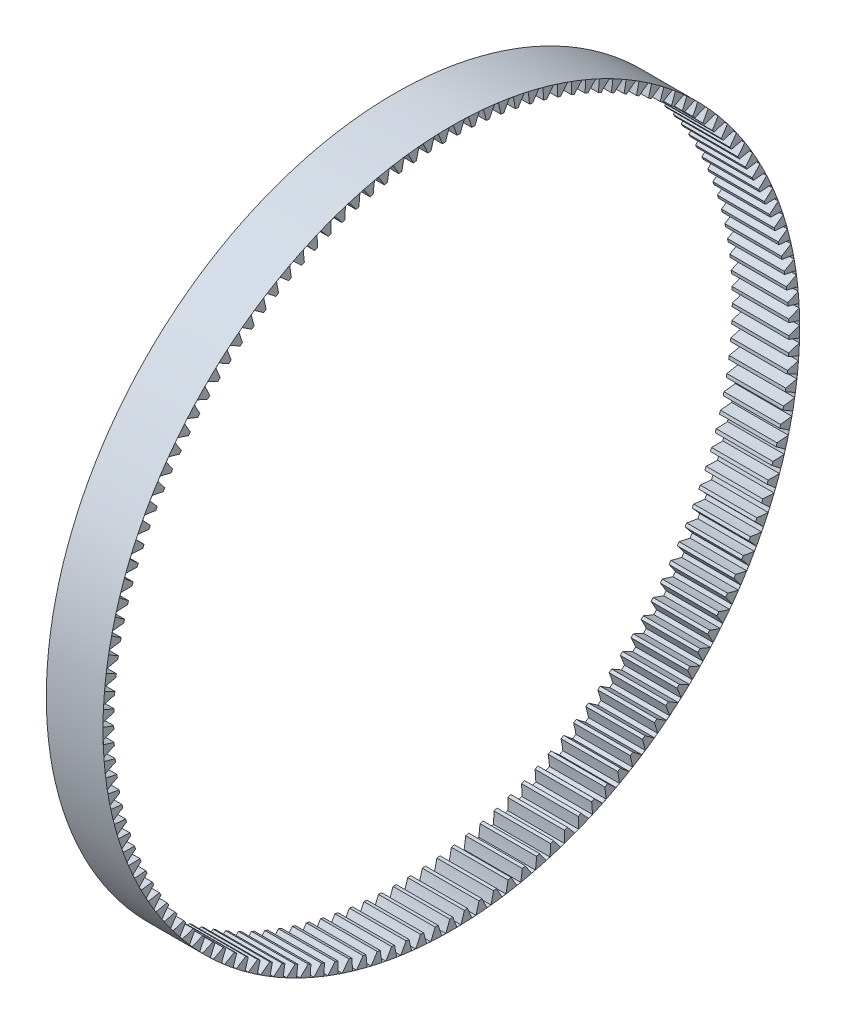
SolidWorks part; units mm, degrees
ref_plane "Plane1" through (0, 0, 0) normal (0, 0, 1) x (1, 0, 0)
ref_plane "Plane2" through (0, 0, 0) normal (0, 1, 0) x (1, 0, 0)
ref_plane "Plane3" through (0, 0, 0) normal (1, 0, 0) x (0, 0, -1)
other "Configuration Table"
sketch "HoldingSke" plane through (0, 0, 0) normal (0, 1, 0) x (1, 0, 0)
  line L0 (0, 0) -> (-0.8192, -0.5736)
  line L1 (-15, 0) -> (100, 0) construction
  line L2 (0, 0) -> (-2.1039, 2.3779)
  line L3 (0, 0) -> (-11.863, 4.5341)
  line L4 (0, 0) -> (-7.0742, 4.9534)
  line L5 (0, 0) -> (-23.7986, -8.8762)
  line L6 (0, 0) -> (-10.5278, -7.1032)
  line L7 (-2.1039, 2.3779) -> (3.3635, 27.1825)
  line L8 (-76.2, 3.3779) -> (-54.61, 3.3779)
  line L9 (-71.009, 38.7566) -> (-53.1078, 45.2721)
  line L10 (-76.2, 71.12) -> (104.1128, 71.12)
  line L11 (0, 0) -> (-12, 0)
  line L12 (-76.2, 101.6) -> (-76.162, 101.6)
  line L13 (24.9733, 27.94) -> (52.9518, 28.4284)
  line L14 (24.9733, 27.94) -> (24.9743, 27.94)
  line L15 (24.9733, 27.94) -> (100.4006, 29.5858)
  circle A0 centre (0, 0) radius 70
  circle A1 centre (0, 0) radius 12.7
  circle A2 centre (0, 0) radius 12.7
  dimension "Num_teeth" = 145
  dimension "Pitch_radius" = 180.3128
  dimension "Width" = 12
sketch "BasProSke" plane through (0, 0, 0) normal (0, 1, 0) x (1, 0, 0)
  line L0 (-10, 0) -> (60, 0) construction
  line L1 (0, 71.5) -> (0, 73.7764)
  line L2 (0, 71.5) -> (12, 71.5)
  line L3 (12, 71.5) -> (12, 73.7764)
  line L4 (12, 73.7764) -> (0, 73.7764)
  dimension "Thickness" = 12
  dimension "Diameter" = 147.5528
revolve "Base-Revolve" add sketch "BasProSke" angle 360 about L0
sketch "TooCutSke" plane through (0, 0, 0) normal (1, 0, 0) x (0, 0, -1)
  line L3 (0.8804, 72.4947) -> (0.8804, 53.6633) construction
  line L4 (0, 0) -> (0, 59.563) construction
  line L5 (0, 0) -> (-1.4803, 68.3115) construction
  line L6 (-33.3648, 60.6063) -> (36.5056, 62.1204) construction
  circle A0 centre (0, 0) radius 72.5 construction
  circle A1 centre (0, 0) radius 73.751 construction
  circle A2 centre (0, 0) radius 61.3149 construction
  circle A3 centre (0, 0) radius 71.4746 construction
  arc A4 (1.2209, 71.4642) -> (0.4185, 73.7498) centre (-33.3648, 60.6063) ccw
  arc A5 (1.2209, 71.4642) -> (-1.2209, 71.4642) centre (0, 0) ccw
  arc A6 (0.4185, 73.7498) -> (-0.4185, 73.7498) centre (0, 0) ccw
  arc A7 (-0.4185, 73.7498) -> (-1.2209, 71.4642) centre (33.3648, 60.6063) ccw
extrude "ToothCut" cut sketch "TooCutSke" along normal through all
fillet "Breaks" [suppressed] radius 0.1
fillet "RootFillets" [suppressed] radius 0.251
pattern_circular "TeethCuts" count 145 every 2.483 about axis through (-10, 0, 0) along (1, 0, 0) of "RootFillets", "Breaks", "ToothCut"
equation "' \"Module@HoldingSke\" = 6.35"
equation "' \"Num_teeth@HoldingSke\" = 24"
equation "' \"Ap@HoldingSke\" =  14.5"
equation "' \"Ap@HoldingSke\" = 14.5"
equation "' \"Width@HoldingSke\" = 12"
equation "' \"Diameter@HoldingSke\" = 8 * 25.4"
equation "' \"Show_teeth@HoldingSke\" = 100"
equation "' \"Backlash@HoldingSke\" = 0.009 * 25.4"
equation "' \"Addendum_fac@HoldingSke\" = 1.0"
equation "' \"Dedendum_fac@HoldingSke\" = 1.25"
equation "' \"Dedendum_add@HoldingSke\" = 0.00005 * 25.4"
equation "' \"Clearance_fac@HoldingSke\" = 0.25"
equation "\"Pitch@HoldingSke\" = 1 / \"Module@HoldingSke\" "
equation "\"Overcut_dia@TooCutSke\" = (\"Num_teeth@HoldingSke\" - 2 * \"Addendum_fac@HoldingSke\") / \"Pitch@HoldingSke\" - 0.002 * 25.4"
equation "\"Pitch_dia@TooCutSke\" = \"Num_teeth@HoldingSke\" / \"Pitch@HoldingSke\""
equation "\"Base_dia@TooCutSke\" = \"Num_teeth@HoldingSke\" / \"Pitch@HoldingSke\" * cos((\"Ap@HoldingSke\"  * 3.14159265 / 180)) * 0.90"
equation "\"Root_dia@TooCutSke\" = \"Num_teeth@HoldingSke\"  / \"Pitch@HoldingSke\" + 2 *  \"Dedendum_fac@HoldingSke\"/ \"Pitch@HoldingSke\" + \"Dedendum_add@HoldingSke\" * 2"
equation "\"Half_ang@TooCutSke\" = 180 / \"Num_teeth@HoldingSke\""
equation "\"Half_CT@TooCutSke\" = \"Num_teeth@HoldingSke\" / \"Pitch@HoldingSke\" * sin((3.14159265 / 2 / \"Num_teeth@HoldingSke\")) / 2 + 10 * \"Backlash@HoldingSke\" / 4"
equation "\"Flank_rad@TooCutSke\" = \"Num_teeth@HoldingSke\" / \"Pitch@HoldingSke\" / 4"
equation "\"Radius@RootFillets\"= \"Clearance_fac@HoldingSke\" / \"Pitch@HoldingSke\" + \"Dedendum_add@HoldingSke\""
equation "\"Break_rad@Breaks\" = 0.02 / \"Pitch@HoldingSke\" * 5"
equation "\"Num_teeth@TeethCuts\" = int( \"Show_teeth@HoldingSke\" ) + 1"
equation "\"Num_teeth@TeethCuts\" = ((sgn( \"Num_teeth@TeethCuts\" - \"Num_teeth@HoldingSke\" )-1)*( \"Num_teeth@TeethCuts\" - \"Num_teeth@HoldingSke\" ))/-2+ \"Num_teeth@HoldingSke\""
equation "\"Num_teeth@TeethCuts\" = ((sgn( \"Num_teeth@TeethCuts\" - 2.0)+1)*( \"Num_teeth@TeethCuts\" - 2.0))/2 +2.0"
equation "\"Angle@TeethCuts\" = 360.0 / \"Num_teeth@HoldingSke\""
equation "\"Diameter@BasProSke\" = \"Num_teeth@HoldingSke\"  / \"Pitch@HoldingSke\" + 2 *  \"Dedendum_fac@HoldingSke\"/ \"Pitch@HoldingSke\" + \"Dedendum_add@HoldingSke\" * 2 + 0.002 * 25.4"
equation "\"Diameter@BasProSke\" = ((sgn( \"Diameter@BasProSke\"  - \"Diameter@HoldingSke\" )+1)*( \"Diameter@BasProSke\"  - \"Diameter@HoldingSke\" ))/2 + \"Diameter@HoldingSke\""
equation "\"Inside_diameter@BasProSke\" =  (\"Num_teeth@HoldingSke\" - 2 * \"Addendum_fac@HoldingSke\") / \"Pitch@HoldingSke\" "
equation "\"Thickness@BasProSke\"  = \"Width@HoldingSke\""
